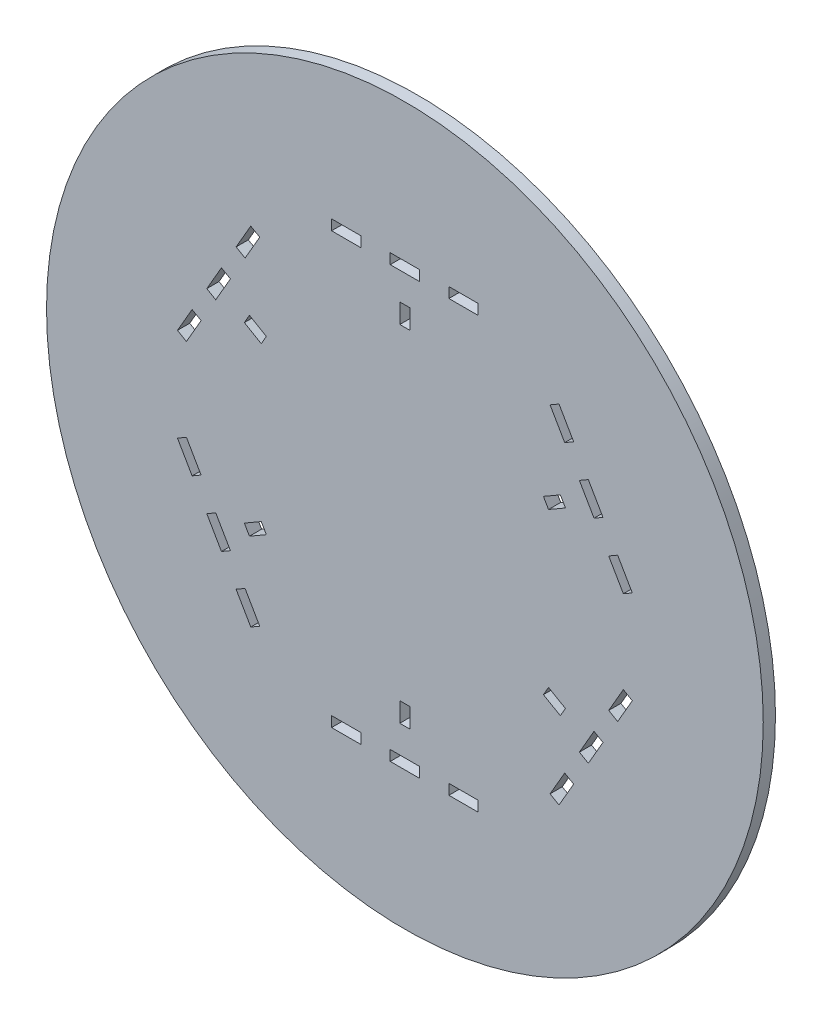
SolidWorks part; units mm, degrees
ref_plane "Front Plane" through (0, 0, 0) normal (0, 0, 1) x (1, 0, 0)
ref_plane "Top Plane" through (0, 0, 0) normal (0, 1, 0) x (1, 0, 0)
ref_plane "Right Plane" through (0, 0, 0) normal (1, 0, 0) x (0, 0, -1)
sketch "Sketch1" plane through (0, 0, 0) normal (0, 0, 1) x (1, 0, 0)
  line L0 (4.5, 67.6125) -> (-4.5, 67.6125)
  line L1 (-4.5, 67.6125) -> (-4.5, 64.4375)
  line L2 (-4.5, 64.4375) -> (4.5, 64.4375)
  line L3 (-13.5, 67.6125) -> (-4.5, 67.6125) construction
  line L4 (-13.5, 67.6125) -> (-22.5, 67.6125)
  line L5 (-13.5, 67.6125) -> (-13.5, 64.4375)
  line L6 (-13.5, 64.4375) -> (-22.5, 64.4375)
  line L7 (-22.5, 67.6125) -> (-22.5, 64.4375)
  line L8 (22.5, 67.6125) -> (22.5, 64.4375)
  line L9 (13.5, 64.4375) -> (22.5, 64.4375)
  line L10 (13.5, 67.6125) -> (13.5, 64.4375)
  line L11 (13.5, 67.6125) -> (22.5, 67.6125)
  line L12 (13.5, 67.6125) -> (4.5, 67.6125) construction
  line L13 (4.5, 67.6125) -> (4.5, 64.4375)
  line L14 (1.5625, 56) -> (-1.5625, 56)
  line L15 (-1.5625, 56) -> (-1.5625, 50)
  line L16 (-1.5625, 50) -> (1.5625, 50)
  line L17 (1.5625, 56) -> (1.5625, 50)
  line L18 (0, 64.4375) -> (0, 56) construction
  line L19 (0, 50) -> (0, 0) construction
  line L20 (60.8041, 29.9091) -> (56.3041, 37.7034)
  line L21 (56.3041, 37.7034) -> (53.5545, 36.1159)
  line L22 (53.5545, 36.1159) -> (58.0545, 28.3216)
  line L23 (51.8041, 45.4976) -> (47.3041, 53.2918)
  line L24 (51.8041, 45.4976) -> (49.0545, 43.9101)
  line L25 (49.0545, 43.9101) -> (44.5545, 51.7043)
  line L26 (47.3041, 53.2918) -> (44.5545, 51.7043)
  line L27 (69.8041, 14.3207) -> (67.0545, 12.7332)
  line L28 (62.5545, 20.5274) -> (67.0545, 12.7332)
  line L29 (65.3041, 22.1149) -> (62.5545, 20.5274)
  line L30 (65.3041, 22.1149) -> (69.8041, 14.3207)
  line L31 (60.8041, 29.9091) -> (58.0545, 28.3216)
  line L32 (49.2787, 26.6468) -> (47.7162, 29.3532)
  line L33 (47.7162, 29.3532) -> (42.52, 26.3532)
  line L34 (42.52, 26.3532) -> (44.0825, 23.6468)
  line L35 (49.2787, 26.6468) -> (44.0825, 23.6468)
  line L36 (51.8041, 45.4976) -> (56.3041, 37.7034) construction
  line L37 (65.3041, 22.1149) -> (60.8041, 29.9091) construction
  line L38 (55.8045, 32.2188) -> (48.4974, 28) construction
  line L39 (56.3041, -37.7034) -> (60.8041, -29.9091)
  line L40 (60.8041, -29.9091) -> (58.0545, -28.3216)
  line L41 (58.0545, -28.3216) -> (53.5545, -36.1159)
  line L42 (65.3041, -22.1149) -> (69.8041, -14.3207)
  line L43 (65.3041, -22.1149) -> (62.5545, -20.5274)
  line L44 (62.5545, -20.5274) -> (67.0545, -12.7332)
  line L45 (69.8041, -14.3207) -> (67.0545, -12.7332)
  line L46 (47.3041, -53.2918) -> (44.5545, -51.7043)
  line L47 (49.0545, -43.9101) -> (44.5545, -51.7043)
  line L48 (51.8041, -45.4976) -> (49.0545, -43.9101)
  line L49 (51.8041, -45.4976) -> (47.3041, -53.2918)
  line L50 (56.3041, -37.7034) -> (53.5545, -36.1159)
  line L51 (47.7162, -29.3532) -> (49.2787, -26.6468)
  line L52 (49.2787, -26.6468) -> (44.0825, -23.6468)
  line L53 (44.0825, -23.6468) -> (42.52, -26.3532)
  line L54 (47.7162, -29.3532) -> (42.52, -26.3532)
  line L55 (65.3041, -22.1149) -> (60.8041, -29.9091) construction
  line L56 (51.8041, -45.4976) -> (56.3041, -37.7034) construction
  line L57 (55.8045, -32.2187) -> (48.4974, -28) construction
  line L58 (-4.5, -67.6125) -> (4.5, -67.6125)
  line L59 (4.5, -67.6125) -> (4.5, -64.4375)
  line L60 (4.5, -64.4375) -> (-4.5, -64.4375)
  line L61 (13.5, -67.6125) -> (22.5, -67.6125)
  line L62 (13.5, -67.6125) -> (13.5, -64.4375)
  line L63 (13.5, -64.4375) -> (22.5, -64.4375)
  line L64 (22.5, -67.6125) -> (22.5, -64.4375)
  line L65 (-22.5, -67.6125) -> (-22.5, -64.4375)
  line L66 (-13.5, -64.4375) -> (-22.5, -64.4375)
  line L67 (-13.5, -67.6125) -> (-13.5, -64.4375)
  line L68 (-13.5, -67.6125) -> (-22.5, -67.6125)
  line L69 (-4.5, -67.6125) -> (-4.5, -64.4375)
  line L70 (-1.5625, -56) -> (1.5625, -56)
  line L71 (1.5625, -56) -> (1.5625, -50)
  line L72 (1.5625, -50) -> (-1.5625, -50)
  line L73 (-1.5625, -56) -> (-1.5625, -50)
  line L74 (13.5, -67.6125) -> (4.5, -67.6125) construction
  line L75 (-13.5, -67.6125) -> (-4.5, -67.6125) construction
  line L76 (0, -64.4375) -> (0, -56) construction
  line L77 (-60.8041, -29.9091) -> (-56.3041, -37.7034)
  line L78 (-56.3041, -37.7034) -> (-53.5545, -36.1159)
  line L79 (-53.5545, -36.1159) -> (-58.0545, -28.3216)
  line L80 (-51.8041, -45.4976) -> (-47.3041, -53.2918)
  line L81 (-51.8041, -45.4976) -> (-49.0545, -43.9101)
  line L82 (-49.0545, -43.9101) -> (-44.5545, -51.7043)
  line L83 (-47.3041, -53.2918) -> (-44.5545, -51.7043)
  line L84 (-69.8041, -14.3207) -> (-67.0545, -12.7332)
  line L85 (-62.5545, -20.5274) -> (-67.0545, -12.7332)
  line L86 (-65.3041, -22.1149) -> (-62.5545, -20.5274)
  line L87 (-65.3041, -22.1149) -> (-69.8041, -14.3207)
  line L88 (-60.8041, -29.9091) -> (-58.0545, -28.3216)
  line L89 (-49.2787, -26.6468) -> (-47.7162, -29.3532)
  line L90 (-47.7162, -29.3532) -> (-42.52, -26.3532)
  line L91 (-42.52, -26.3532) -> (-44.0825, -23.6468)
  line L92 (-49.2787, -26.6468) -> (-44.0825, -23.6468)
  line L93 (-51.8041, -45.4976) -> (-56.3041, -37.7034) construction
  line L94 (-65.3041, -22.1149) -> (-60.8041, -29.9091) construction
  line L95 (-55.8045, -32.2188) -> (-48.4974, -28) construction
  line L96 (-56.3041, 37.7034) -> (-60.8041, 29.9091)
  line L97 (-60.8041, 29.9091) -> (-58.0545, 28.3216)
  line L98 (-58.0545, 28.3216) -> (-53.5545, 36.1159)
  line L99 (-65.3041, 22.1149) -> (-69.8041, 14.3207)
  line L100 (-65.3041, 22.1149) -> (-62.5545, 20.5274)
  line L101 (-62.5545, 20.5274) -> (-67.0545, 12.7332)
  line L102 (-69.8041, 14.3207) -> (-67.0545, 12.7332)
  line L103 (-47.3041, 53.2918) -> (-44.5545, 51.7043)
  line L104 (-49.0545, 43.9101) -> (-44.5545, 51.7043)
  line L105 (-51.8041, 45.4976) -> (-49.0545, 43.9101)
  line L106 (-51.8041, 45.4976) -> (-47.3041, 53.2918)
  line L107 (-56.3041, 37.7034) -> (-53.5545, 36.1159)
  line L108 (-47.7162, 29.3532) -> (-49.2787, 26.6468)
  line L109 (-49.2787, 26.6468) -> (-44.0825, 23.6468)
  line L110 (-44.0825, 23.6468) -> (-42.52, 26.3532)
  line L111 (-47.7162, 29.3532) -> (-42.52, 26.3532)
  line L112 (-65.3041, 22.1149) -> (-60.8041, 29.9091) construction
  line L113 (-51.8041, 45.4976) -> (-56.3041, 37.7034) construction
  line L114 (-55.8045, 32.2188) -> (-48.4974, 28) construction
  circle A0 centre (0, 0) radius 110
  point P3 (0, 67.6125)
  point P13 (0, 64.4375)
  point P18 (0, 50)
  point P19 (0, 56)
  point P31 (58.5541, 33.8062)
  point P41 (55.8045, 32.2188)
  point P46 (43.3013, 25)
  point P47 (48.4974, 28)
  point P53 (58.5541, -33.8063)
  point P63 (55.8045, -32.2187)
  point P68 (43.3013, -25)
  point P69 (48.4974, -28)
  point P75 (0, -67.6125)
  point P85 (0, -64.4375)
  point P90 (0, -50)
  point P91 (0, -56)
  point P97 (-58.5541, -33.8063)
  point P107 (-55.8045, -32.2188)
  point P112 (-43.3013, -25)
  point P113 (-48.4974, -28)
  point P119 (-58.5541, 33.8063)
  point P129 (-55.8045, 32.2188)
  point P134 (-43.3013, 25)
  point P135 (-48.4974, 28)
  point P138 (0, 0)
  dimension "D8" = 220
  dimension "D1" = 3.175
  dimension "D2" = 9
  dimension "D3" = 1.5625
  dimension "D4" = 6
  dimension "D5" = 8.4375
  dimension "D6" = 50
  dimension "D7" = 6
extrude "Boss-Extrude1" add sketch "Sketch1" along normal mid plane 3.75
